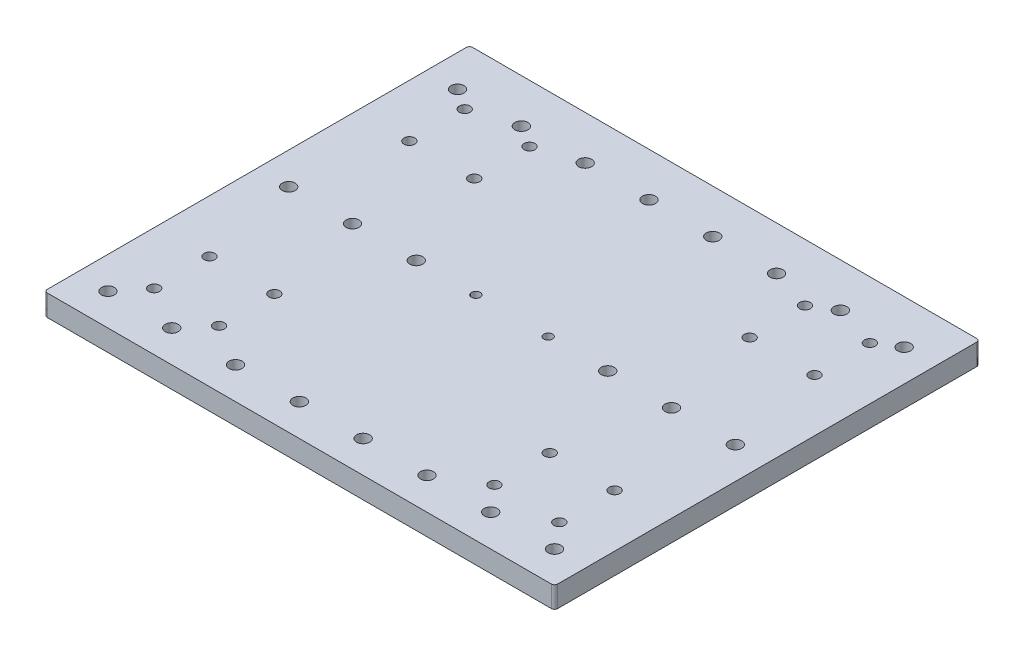
SolidWorks part; units mm, degrees
ref_plane "Front Plane" through (0, 0, 0) normal (0, 0, 1) x (1, 0, 0)
ref_plane "Top Plane" through (0, 0, 0) normal (0, 1, 0) x (1, 0, 0)
ref_plane "Right Plane" through (0, 0, 0) normal (1, 0, 0) x (0, 0, -1)
sketch "Sketch1" plane through (0, 0, 0) normal (0, 1, 0) x (1, 0, 0)
  line L1 (-120, -100) -> (120, -100)
  line L2 (-120, -100) -> (-120, 100)
  line L3 (-120, 100) -> (120, 100)
  line L4 (120, -100) -> (120, 100)
  line L5 (-120, -100) -> (120, 100) construction
  line L6 (-120, 100) -> (120, -100) construction
  point P0 (0, 0)
  dimension "D1" = 240
  dimension "D2" = 200
extrude "Boss-Extrude1" add sketch "Sketch1" along normal mid plane 10
sketch "Sketch2" plane through (0, 5, 0) normal (0, 1, 0) x (1, 0, 0)
  line L5 (-80, 100) -> (-80, -100)
  line L6 (-80, 100) -> (-80, -100) construction
  line L8 (80, -100) -> (80, 100)
  line L9 (80, -100) -> (80, 100) construction
  line L11 (120, 60) -> (-120, 60)
  line L12 (120, 60) -> (-120, 60) construction
  line L14 (-120, -60) -> (120, -60)
  line L15 (-120, -60) -> (120, -60) construction
  line L16 (-95.25, 73) -> (-64.75, 73) construction
  line L17 (-95.25, 73) -> (-95.25, 47) construction
  line L18 (-95.25, 47) -> (-64.75, 47) construction
  line L19 (-64.75, 73) -> (-64.75, 47) construction
  line L20 (-95.25, 73) -> (-64.75, 47) construction
  line L21 (-95.25, 47) -> (-64.75, 73) construction
  line L22 (64.75, 47) -> (95.25, 47) construction
  line L23 (64.75, 47) -> (64.75, 73) construction
  line L24 (64.75, 73) -> (95.25, 73) construction
  line L25 (95.25, 47) -> (95.25, 73) construction
  line L26 (64.75, 47) -> (95.25, 73) construction
  line L27 (64.75, 73) -> (95.25, 47) construction
  line L28 (64.75, -47) -> (95.25, -47) construction
  line L29 (64.75, -47) -> (64.75, -73) construction
  line L30 (64.75, -73) -> (95.25, -73) construction
  line L31 (95.25, -47) -> (95.25, -73) construction
  line L32 (64.75, -47) -> (95.25, -73) construction
  line L33 (64.75, -73) -> (95.25, -47) construction
  line L34 (-95.25, -73) -> (-64.75, -73) construction
  line L35 (-95.25, -73) -> (-95.25, -47) construction
  line L36 (-95.25, -47) -> (-64.75, -47) construction
  line L37 (-64.75, -73) -> (-64.75, -47) construction
  line L38 (-95.25, -73) -> (-64.75, -47) construction
  line L39 (-95.25, -47) -> (-64.75, -73) construction
  circle A0 centre (-95.25, 73) radius 2.55
  circle A1 centre (-95.25, 47) radius 2.55
  circle A2 centre (-64.75, 73) radius 2.55
  circle A3 centre (-64.75, 47) radius 2.55
  circle A4 centre (-95.25, -47) radius 2.55
  circle A5 centre (-95.25, -73) radius 2.55
  circle A6 centre (-64.75, -73) radius 2.55
  circle A7 centre (-64.75, -47) radius 2.55
  circle A8 centre (95.25, -47) radius 2.55
  circle A9 centre (64.75, -47) radius 2.55
  circle A10 centre (64.75, -73) radius 2.55
  circle A11 centre (95.25, -73) radius 2.55
  circle A12 centre (64.75, 73) radius 2.55
  circle A13 centre (64.75, 47) radius 2.55
  circle A14 centre (95.25, 73) radius 2.55
  circle A15 centre (95.25, 47) radius 2.55
  point P0 (-80, 60)
  point P13 (80, 60)
  point P18 (80, -60)
  point P23 (-80, -60)
  dimension "D13" = 5.1
  dimension "D14" = 5.1
  dimension "D15" = 5.1
  dimension "D16" = 5.1
  dimension "D17" = 5.1
  dimension "D18" = 5.1
  dimension "D19" = 5.1
  dimension "D20" = 5.1
  dimension "D21" = 5.1
  dimension "D22" = 5.1
  dimension "D23" = 5.1
  dimension "D24" = 5.1
  dimension "D25" = 5.1
  dimension "D26" = 5.1
  dimension "D27" = 5.1
  dimension "D28" = 5.1
  dimension "D1" = 40
  dimension "D5" = 30.5
  dimension "D6" = 26
  dimension "D7" = 30.5
  dimension "D8" = 26
  dimension "D9" = 26
  dimension "D10" = 30.5
  dimension "D11" = 26
  dimension "D12" = 30.5
  dimension "D2" = 40
  dimension "D3" = 40
  dimension "D4" = 40
extrude "Cut-Extrude1" cut sketch "Sketch2" against normal through all
sketch "Sketch3" plane through (0, 5, 0) normal (0, 1, 0) x (1, 0, 0)
  line L3 (-17, 0) -> (17, 0) construction
  circle A0 centre (-17, 0) radius 2.05
  circle A1 centre (17, 0) radius 2.05
  point P0 (0, 0)
  dimension "D3" = 4.1
  dimension "D4" = 4.1
  dimension "D1" = 34
extrude "Cut-Extrude2" cut sketch "Sketch3" against normal through all
sketch "Sketch4" plane through (0, 5, 0) normal (0, 1, 0) x (1, 0, 0)
  line L0 (-105, 100) -> (-105, -100) construction
  line L1 (120, 100) -> (-120, 100) construction
  line L2 (-120, -100) -> (120, -100) construction
  line L3 (-120, 100) -> (-120, -100) construction
  line L4 (-75, 100) -> (-75, -100) construction
  line L5 (-45, 100) -> (-45, -100) construction
  line L6 (-15, 100) -> (-15, -100) construction
  line L7 (15, 100) -> (15, -100) construction
  line L8 (45, 100) -> (45, -100) construction
  line L9 (75, 100) -> (75, -100) construction
  line L10 (105, 100) -> (105, -100) construction
  line L11 (-120, -85) -> (120, -85) construction
  line L12 (-120, 100) -> (-120, -100) construction
  line L13 (120, -100) -> (120, 100) construction
  line L14 (-120, 79.3935) -> (120, 79.3935) construction
  line L15 (-120, 0) -> (120, 0) construction
  circle A0 centre (-105, 79.3935) radius 3.05
  circle A1 centre (-75, 79.3935) radius 3.05
  circle A2 centre (-45, 79.3935) radius 3.05
  circle A3 centre (-15, 79.3935) radius 3.05
  circle A4 centre (15, 79.3935) radius 3.05
  circle A5 centre (45, 79.3935) radius 3.05
  circle A6 centre (75, 79.3935) radius 3.05
  circle A7 centre (105, 79.3935) radius 3.05
  circle A8 centre (-105, 0) radius 3.05
  circle A9 centre (-105, -85) radius 3.05
  circle A10 centre (-75, 0) radius 3.05
  circle A11 centre (-45, 0) radius 3.05
  circle A14 centre (45, 0) radius 3.05
  circle A15 centre (75, 0) radius 3.05
  circle A16 centre (105, 0) radius 3.05
  circle A17 centre (-75, -85) radius 3.05
  circle A18 centre (-45, -85) radius 3.05
  circle A19 centre (-15, -85) radius 3.05
  circle A20 centre (15, -85) radius 3.05
  circle A21 centre (45, -85) radius 3.05
  circle A22 centre (75, -85) radius 3.05
  circle A23 centre (105, -85) radius 3.05
  circle A24 centre (-15, 0) radius 3.05 [skipped]
  circle A25 centre (15, 0) radius 3.05 [skipped]
  point P6 (-120, 0)
  dimension "D3" = 6.1
  dimension "D4" = 6.1
  dimension "D5" = 6.1
  dimension "D1" = 15
  dimension "D2" = 15
  dimension "D6" = 8
extrude "Cut-Extrude3" cut sketch "Sketch4" against normal through all
fillet "Fillet1" radius 1.5 4 edges at (-120, 0, -100) (120, 0, -100) (-120, 0, 100) (120, 0, 100)
equation "\"D4@Sketch4\"=\"D3@Sketch4\""
equation "\"D5@Sketch4\"=\"D3@Sketch4\""
